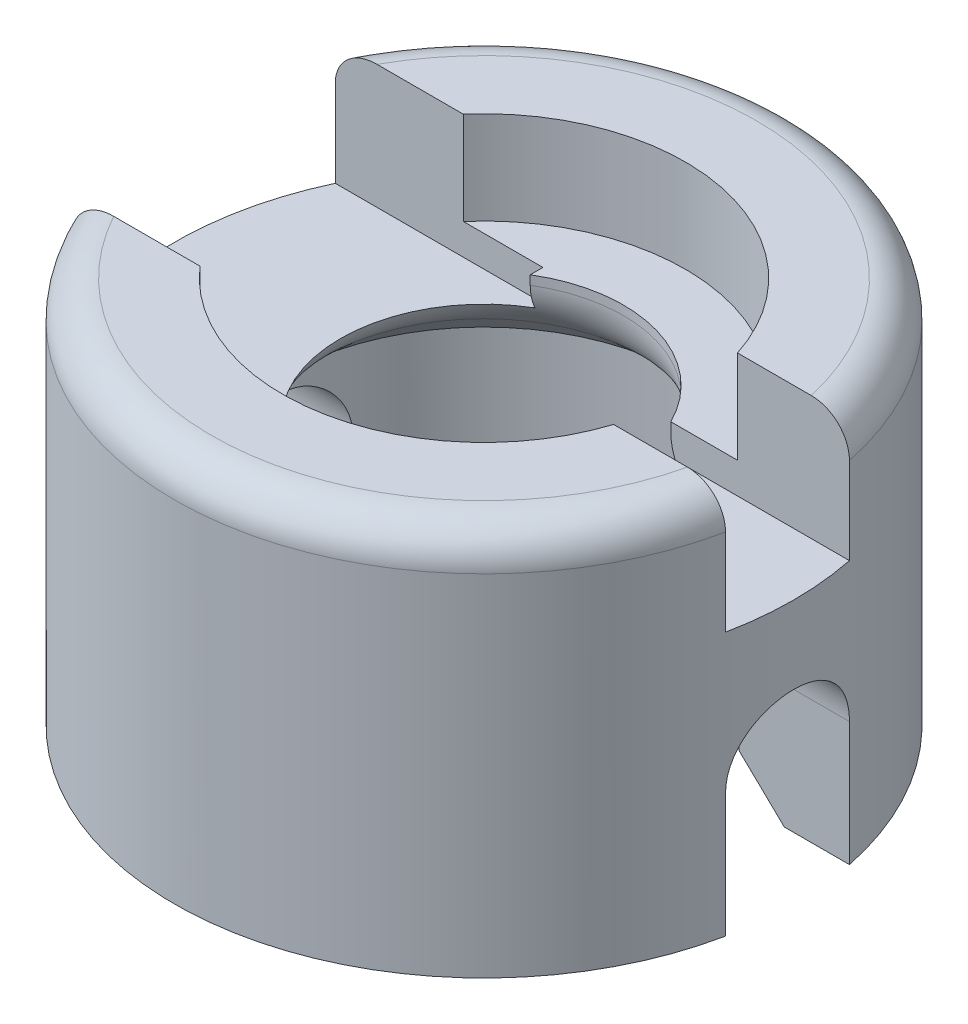
SolidWorks part; units mm, degrees
material "ABS"
ref_plane "Alzado" through (0, 0, 0) normal (0, 0, 1) x (1, 0, 0)
ref_plane "Planta" through (0, 0, 0) normal (0, 1, 0) x (1, 0, 0)
ref_plane "Vista lateral" through (0, 0, 0) normal (1, 0, 0) x (0, 0, -1)
sketch "Croquis1" plane through (0, 0, 0) normal (0, 1, 0) x (1, 0, 0)
  circle A0 centre (0, 0) radius 3.275
  circle A1 centre (0, 0) radius 5
  dimension "D1" = 10
  dimension "D2" = 6.55
extrude "Saliente-Extruir1" add sketch "Croquis1" along normal blind 3.25
sketch "Croquis2" plane through (0, 0, 0) normal (0, 0, 1) x (1, 0, 0)
  line L0 (-5, 3.25) -> (-5, 4.25)
  line L1 (-5, 4.25) -> (-2.25, 4.25)
  line L2 (-2.25, 4.25) -> (-2.25, 4.15)
  line L3 (-2.25, 4.15) -> (-3.275, 3.25)
  line L4 (5, 3.25) -> (-5, 3.25) construction
  line L5 (0, 0) -> (0, 6.8987) construction
  line L6 (-5, 3.25) -> (-3.275, 3.25)
  dimension "D1" = 4.5
  dimension "D2" = 0.1
  dimension "D3" = 2.75
  dimension "D4" = 1
revolve "Revolución1" add sketch "Croquis2" angle 360 about L5
sketch "Croquis3" plane through (0, 4.25, 0) normal (0, 1, 0) x (1, 0, 0)
  circle A0 centre (0, 0) radius 2.25
  circle A1 centre (0, 0) radius 5
  circle A2 centre (0, 0) radius 5 construction
  circle A3 centre (0, 0) radius 2.25 construction
extrude "Saliente-Extruir2" add sketch "Croquis3" along normal blind 2
fillet "Redondeo1" radius 0.6 1 edges at (0, 6.25, 5)
sketch "Croquis4" plane through (0, 6.25, 0) normal (0, 1, 0) x (1, 0, 0)
  circle A0 centre (0, 0) radius 3.2
  dimension "D1" = 6.4
fillet "Redondeo2" radius 1 1 edges at (0, 4.15, -2.25)
chamfer "Chaflán1" distance 0.7 angle 45 1 edges at (0, 0, 3.275)
chamfer "Chaflán2" distance 0.5 angle 45 1 edges at (0, 6.25, 2.25)
sketch "Sketch1" plane through (0, 6.25, 0) normal (0, 1, 0) x (1, 0, 0)
  line L1 (6.9669, 1) -> (-6.9669, 1)
  line L2 (6.9669, 1) -> (6.9669, -1)
  line L3 (6.9669, -1) -> (-6.9669, -1)
  line L4 (-6.9669, 1) -> (-6.9669, -1)
  line L5 (6.9669, 1) -> (-6.9669, -1) construction
  line L6 (6.9669, -1) -> (-6.9669, 1) construction
  point P0 (0, 0)
  dimension "D1" = 2
extrude "Cut-Extrude1" cut sketch "Sketch1" against normal blind 2
sketch "Sketch2" plane through (0, 6.25, 0) normal (0, 1, 0) x (1, 0, 0)
  circle A0 centre (0, 0) radius 3.25
  dimension "D1" = 6.5
extrude "Cut-Extrude2" cut sketch "Sketch2" against normal blind 1.5
sketch "Sketch3" plane through (0, 0, 0) normal (0, -1, 0) x (1, 0, 0)
  line L1 (8.6309, -1) -> (-8.6309, -1)
  line L2 (8.6309, -1) -> (8.6309, 1)
  line L3 (8.6309, 1) -> (-8.6309, 1)
  line L4 (-8.6309, -1) -> (-8.6309, 1)
  line L5 (8.6309, -1) -> (-8.6309, 1) construction
  line L6 (8.6309, 1) -> (-8.6309, -1) construction
  point P0 (0, 0)
  dimension "D1" = 2
extrude "Cut-Extrude3" cut sketch "Sketch3" against normal blind 3
sketch "Sketch4" plane through (0, 6.25, 0) normal (0, 1, 0) x (1, 0, 0)
  line L1 (-5.9099, 2.125) -> (-1.1736, 2.125)
  line L2 (-5.9099, 2.125) -> (-5.9099, -2.125)
  line L3 (-5.9099, -2.125) -> (-1.1736, -2.125)
  line L4 (-1.1736, 2.125) -> (-1.1736, -2.125)
  point P6 (-1.1736, 0)
  dimension "D1" = 4.25
extrude "Cut-Extrude4" cut sketch "Sketch4" against normal up to surface (2 mm away) up to face at (3.5751, 4.25, 0)
fillet "Fillet1" radius 1 4 edges at (4.0088, 3, -1) (-4.0088, 3, -1) (4.0088, 3, 1) (-4.0088, 3, 1)
